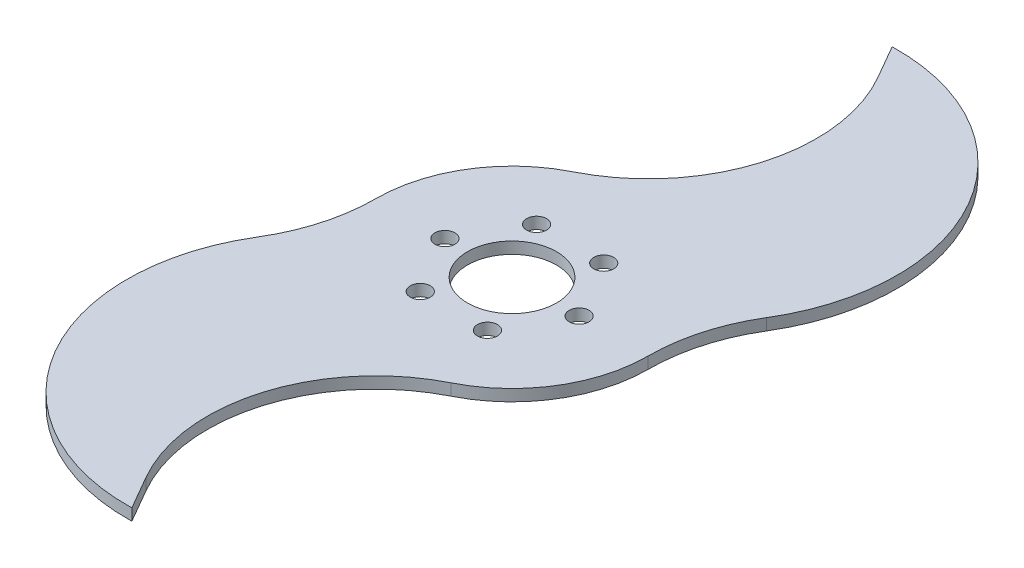
SolidWorks part; units mm, degrees
ref_plane "Front Plane" through (0, 0, 0) normal (0, 0, 1) x (1, 0, 0)
ref_plane "Top Plane" through (0, 0, 0) normal (0, 1, 0) x (1, 0, 0)
ref_plane "Right Plane" through (0, 0, 0) normal (1, 0, 0) x (0, 0, -1)
ref_axis "Axis1" through (0, -0.15, 0) along (0, 1, 0)
sketch "Sketch1" plane through (0, 0, 0) normal (0, 1, 0) x (1, 0, 0)
  line L1 (17.5, 0) -> (8.75, 15.1554) construction
  line L2 (8.75, 15.1554) -> (-8.75, 15.1554) construction
  line L3 (-8.75, 15.1554) -> (-17.5, 0) construction
  line L4 (-17.5, 0) -> (-8.75, -15.1554) construction
  line L5 (-8.75, -15.1554) -> (8.75, -15.1554) construction
  line L6 (8.75, -15.1554) -> (17.5, 0) construction
  circle A0 centre (0, 0) radius 15.1554 construction
  circle A1 centre (8.75, 15.1554) radius 2.6
  circle A2 centre (17.5, 0) radius 2.6
  circle A3 centre (8.75, -15.1554) radius 2.6
  circle A4 centre (-8.75, -15.1554) radius 2.6
  circle A5 centre (-17.5, 0) radius 2.6
  circle A6 centre (-8.75, 15.1554) radius 2.6
  circle A7 centre (0, 0) radius 11.6
  circle A8 centre (0, 0) radius 101.6 construction
  dimension "D1" = 5.2
  dimension "D2" = 23.2
  dimension "D3" = 203.2
  dimension "D4" = 35
sketch "Sketch2" plane through (0, 0, 0) normal (0, 1, 0) x (1, 0, 0)
  line L0 (0, -1000) -> (0, 49000) construction
  line L1 (-2.5, 101.5692) -> (2.5, 92.909)
  line L2 (0, 0) -> (35355.3391, 35355.3391) construction
  line L3 (-15.872, 31.7542) -> (15.872, -31.7542) construction
  line L4 (-1000, 0) -> (49000, 0) construction
  circle A0 centre (0, 0) radius 101.6 construction
  arc A1 (-2.5, 101.5692) -> (42.263, 24.0679) centre (-1.2458, 50.6159) cw
  circle A3 centre (0, 0) radius 79.6 construction
  circle A5 centre (0, 0) radius 35.5 construction
  arc A20 (-2.5, 101.5692) -> (0, 0) centre (-49.5947, 49.5947) cw construction
  arc A21 (2.5, 92.909) -> (-15.872, 31.7542) centre (-35.4793, 70.9816) cw
  arc A23 (42.263, 24.0679) -> (35.5, 0) centre (81.7072, 0) ccw
  arc A24 (-15.872, 31.7542) -> (35.5, 0) centre (0, 0) ccw
  point P7 (0, 97.2391)
  point P16 (-79.6, 0)
  point P17 (-101.6, 0)
  point P21 (35.5, 0)
  point P25 (32.5, 0)
  dimension "D3" = 45
  dimension "D1" = 30
  dimension "D2" = 22
  dimension "D4" = 10
  dimension "D5" = 18
  dimension "D6" = 25
extrude "Boss-Extrude1" add sketch "Sketch2" along normal blind 3.02
pattern_circular "CirPattern1" count 2 over 360 about axis through (0, -0.15, 0) along (0, 1, 0) of bodies 101
combine bodies "Combine1" bodies to combine 101 102
extrude "Cut-Extrude3" cut sketch "Sketch1" along normal through all
